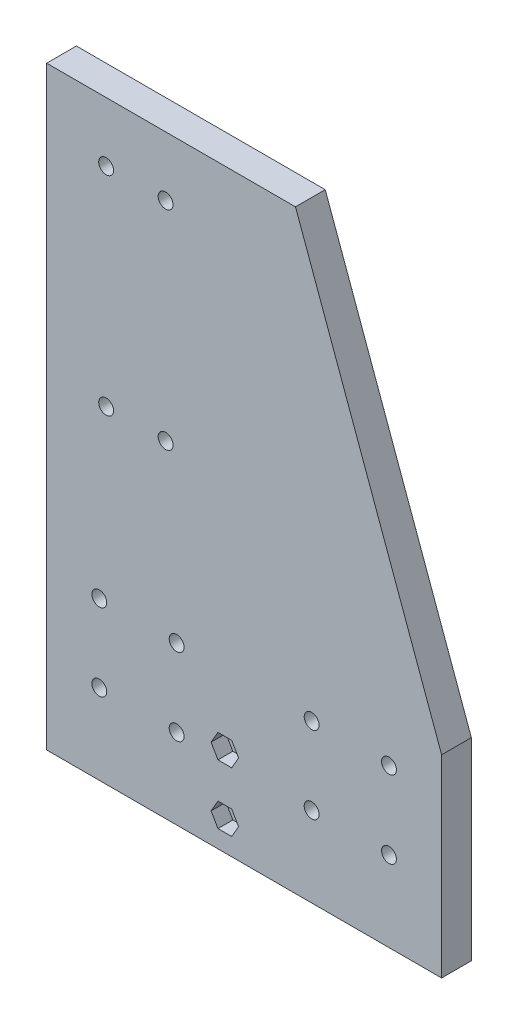
SolidWorks part; units mm, degrees
other "Markup1"
sketch "Sketch3" plane through (0, 200, 35) normal (-0.0073, 0.0178, 0.9998) x (0.9997, -0.0226, 0.0077)
ref_plane "Front Plane" through (0, 0, 0) normal (0, 0, 1) x (1, 0, 0)
ref_plane "Top Plane" through (0, 0, 0) normal (0, 1, 0) x (1, 0, 0)
ref_plane "Right Plane" through (0, 0, 0) normal (1, 0, 0) x (0, 0, -1)
sketch "Sketch1" plane through (0, 0, 0) normal (0, 0, 1) x (1, 0, 0)
  line L0 (66.4, -5.8678) -> (66.4, 56.1407) construction
  line L5 (0, 0) -> (132.8, 0)
  line L6 (0, 0) -> (0, 200)
  line L7 (0, 200) -> (83.664, 200)
  line L8 (132.8, 0) -> (132.8, 65)
  line L9 (71.4, 57.9012) -> (71.4, -9.8319) construction
  line L23 (102.1, 57.9012) -> (102.1, -7.5742) construction
  line L24 (83.9369, 40) -> (119.8285, 40) construction
  line L25 (52.3456, 19.92) -> (67.8875, 19.92) construction
  line L26 (64.535, 29.92) -> (62.2225, 33.9254)
  line L27 (62.2225, 33.9254) -> (57.5975, 33.9254)
  line L28 (57.5975, 33.9254) -> (55.285, 29.92)
  line L29 (55.285, 29.92) -> (57.5975, 25.9146)
  line L30 (57.5975, 25.9146) -> (62.2225, 25.9146)
  line L31 (62.2225, 25.9146) -> (64.535, 29.92)
  line L32 (62.2225, 13.9254) -> (64.535, 9.92)
  line L33 (57.5975, 13.9254) -> (62.2225, 13.9254)
  line L34 (55.285, 9.92) -> (57.5975, 13.9254)
  line L35 (57.5975, 5.9146) -> (55.285, 9.92)
  line L36 (62.2225, 5.9146) -> (57.5975, 5.9146)
  line L37 (64.535, 9.92) -> (62.2225, 5.9146)
  line L38 (132.8, 65) -> (83.664, 200)
  circle A12 centre (115.1, 27) radius 2.5
  circle A13 centre (89.1, 27) radius 2.5
  circle A14 centre (115.1, 53) radius 2.5
  circle A15 centre (89.1, 53) radius 2.5
  circle A16 centre (17.7, 53) radius 2.5
  circle A17 centre (17.7, 27) radius 2.5
  circle A18 centre (43.7, 27) radius 2.5
  circle A19 centre (43.7, 53) radius 2.5
  circle A20 centre (59.91, 29.92) radius 4.0054 construction
  circle A21 centre (59.91, 29.92) radius 2.5
  circle A23 centre (59.91, 9.92) radius 2.5
  dimension "D4" = 5
  dimension "D13" = 5
  dimension "D1" = 200
  dimension "D2" = 132.8
  dimension "D3" = 26
  dimension "D5" = 61.4
  dimension "D6" = 30.7
  dimension "D7" = 27
  dimension "D8" = 13
  dimension "D9" = 29.92
  dimension "D10" = 10
  dimension "D11" = 9.25
  dimension "D12" = 11.49
  dimension "D14" = 65
  dimension "D15" = 20
  dimension "D16" = 9.92
extrude "Boss-Extrude1" add sketch "Sketch1" along normal blind 10 contours L8 L38 L7 L6 L5 A19 A17 A16 A14 A13 A12 L32 L37 L36 L35 L34 L33 L31 L30 L29 L28 L27 L26 A15 A18 | L30 L31 L26 L27 L28 L29 A21 | L37 L32 L33 L34 L35 L36 region at (59.2103, 92.8578, 0) region at (63.2728, 27.9785, 0) region at (63.2728, 11.8615, 0)
extrude "Cut-Extrude1" cut sketch "Sketch1<3>" along normal blind 5 from offset 5 contours L30 L31 L26 L27 L28 L29 A21 | L37 L32 L33 L34 L35 L36 region at (63.2728, 27.9785, 0) region at (63.2728, 11.8615, 0)
sketch "Sketch1<3>" plane through (0, 0, 0) normal (0, 0, 1) x (1, 0, 0) same geometry as "Sketch1"
sketch "Sketch4" plane through (0, 0, 0) normal (0, 0, -1) x (-1, 0, 0)
  line L0 (0, 0) -> (0, 200) construction
  line L1 (0, 200) -> (-83.664, 200) construction
  line L2 (-40, 180) -> (-40, 110) construction
  circle A0 centre (-20, 180) radius 2.5
  circle A2 centre (-40, 180) radius 2.5
  circle A3 centre (-40, 110) radius 2.5
  circle A4 centre (-20, 110) radius 2.5
  dimension "D1" = 5
  dimension "D2" = 20
  dimension "D3" = 20
  dimension "D4" = 20
  dimension "D5" = 2
  dimension "D6" = 70
extrude "Cut-Extrude2" cut sketch "Sketch4" against normal through all
